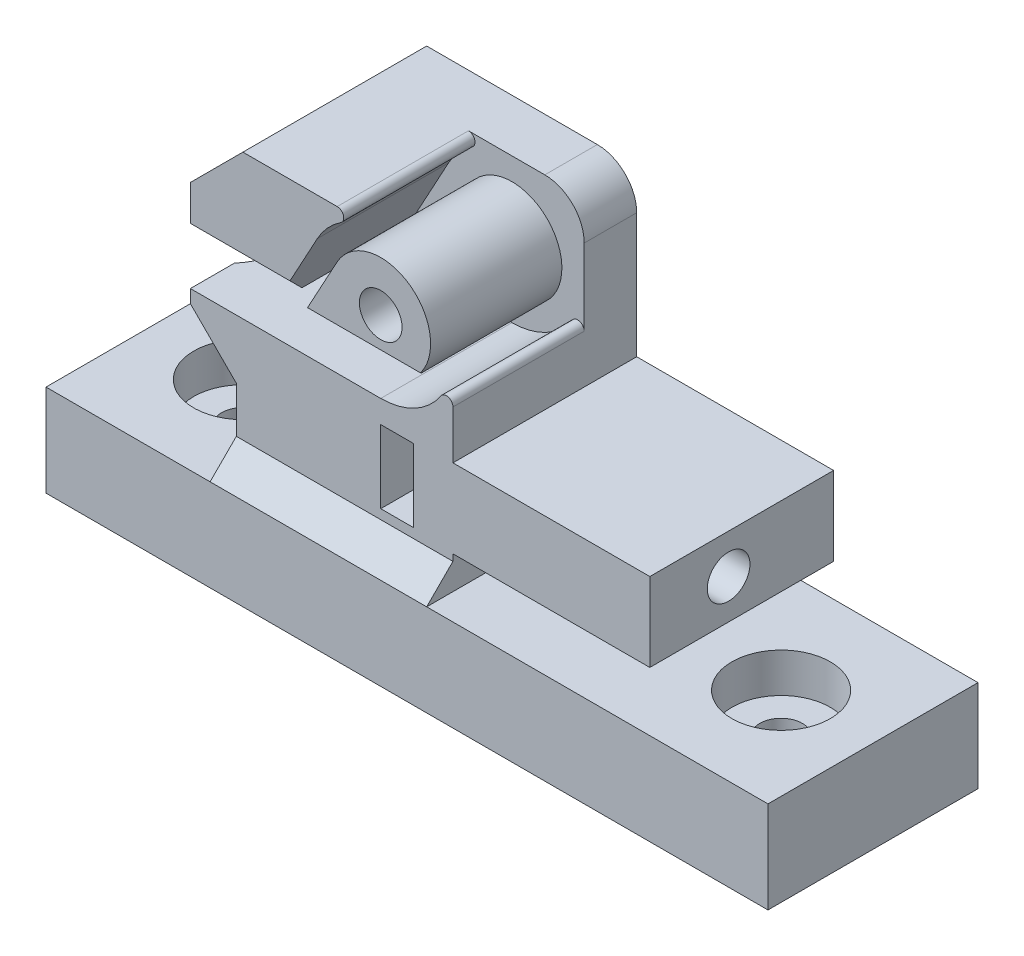
SolidWorks part; units mm, degrees
ref_plane "Front Plane" through (0, 0, 0) normal (0, 0, 1) x (1, 0, 0)
ref_plane "Top Plane" through (0, 0, 0) normal (0, 1, 0) x (1, 0, 0)
ref_plane "Right Plane" through (0, 0, 0) normal (1, 0, 0) x (0, 0, -1)
ref_plane "Plane1" [suppressed] through (25.5, 0, 0) normal (1, 0, 0) x (0, 0, -1)
sketch "Sketch4" plane through (0, 0, 0) normal (0, 0, 1) x (1, 0, 0)
  line L0 (-3.5, -0.0261) -> (-3.5, 6.9739)
  line L1 (-3.5, 6.9739) -> (9, 6.9739)
  line L4 (9, 6.9739) -> (9, 12.4739)
  line L5 (5.5, 27.9739) -> (5.5, 12.4739)
  line L8 (5.5, 27.9739) -> (25.5, 27.9739)
  line L9 (25.5, 27.9739) -> (25.5, 15.4739)
  line L10 (25.5, 15.4739) -> (40.5, 15.4739)
  line L11 (40.5, 15.4739) -> (40.5, 9.4739)
  line L12 (40.5, 9.4739) -> (25.5, 9.4739)
  line L13 (25.5, 9.4739) -> (25.5, 6.9739)
  line L14 (9, 12.4739) -> (5.5, 12.4739)
  line L16 (25.5, 6.9739) -> (51.5, 6.9739)
  line L17 (51.5, 6.9739) -> (51.5, -0.0261)
  line L18 (51.5, -0.0261) -> (-3.5, -0.0261)
  dimension "D1" = 7
  dimension "D2" = 3.5
  dimension "D3" = 26
  dimension "D4" = 29
  dimension "D5" = 28
  dimension "D6" = 15
  dimension "D10" = 6
  dimension "D11" = 12.5
  dimension "D12" = 20
  dimension "D13" = 15.5
extrude "Boss-Extrude1" add sketch "Sketch4" against normal blind 16 separate body
sketch "Sketch6" plane through (0, 0, 0) normal (0, 0, 1) x (1, 0, 0)
  line L0 (5.5, 19.2739) -> (12, 19.2739)
  line L1 (13.6088, 18.6739) -> (16.6615, 24.2889)
  line L2 (25.5, 27.9739) -> (20, 27.9739)
  line L3 (20, 18.6739) -> (13.6088, 18.6739)
  line L4 (25.5, 27.9739) -> (25.5, 22.4736)
  line L6 (5.5, 27.9739) -> (5.5, 12.4739) construction
  line L7 (25.5, 27.9739) -> (5.5, 27.9739) construction
  line L8 (5.5, 19.2739) -> (5.5, 16.9739)
  line L9 (12, 19.2739) -> (15.1679, 25.1009)
  line L10 (5.5, 16.9739) -> (20, 16.9739)
  line L15 (25.5, 15.4739) -> (25.5, 27.9739) construction
  arc A0 (20, 18.6739) -> (16.6615, 24.2889) centre (20, 22.4739) ccw
  arc A1 (20, 27.9739) -> (15.1679, 25.1009) centre (20, 22.4739) ccw
  arc A2 (20, 16.9739) -> (25.5, 22.4736) centre (20, 22.4739) ccw
  dimension "D1" = 1.7
  dimension "D2" = 5.5
  dimension "D4" = 6.5
  dimension "D3" = 2.3
extrude "Cut-Extrude1" cut sketch "Sketch6" against normal blind 14 from offset 2
sketch "Sketch7" plane through (40.5, 0, 0) normal (1, 0, 0) x (0, 0, -1)
  line L2 (0, 9.4739) -> (0, 15.4739) construction
  line L3 (16, 9.4739) -> (0, 9.4739) construction
  circle A0 centre (8, 12.4739) radius 1.625
  point P8 (0, 12.4739)
  point P10 (8, 9.4739)
  dimension "D1" = 3.25
extrude "Cut-Extrude2" cut sketch "Sketch7" against normal through all
sketch "Sketch8" plane through (40.5, 0, 0) normal (1, 0, 0) x (0, 0, -1)
  line L0 (0, 15.2489) -> (0, 9.6989)
  line L1 (0, 9.6989) -> (10.869, 9.6989)
  line L2 (5.131, 9.6989) -> (5.131, 15.2489) construction
  line L3 (0, 15.2489) -> (10.869, 15.2489)
  line L4 (10.869, 9.6989) -> (10.869, 15.2489)
  line L5 (5.131, 9.6989) -> (10.869, 15.2489) construction
  line L6 (5.131, 15.2489) -> (10.869, 9.6989) construction
  line L8 (0, 9.4739) -> (0, 15.4739) construction
  point P0 (8, 12.4739)
  dimension "D1" = 5.55
extrude "Cut-Extrude3" cut sketch "Sketch8" against normal blind 2.5 from offset 18 offset against normal yes
sketch "Sketch9" plane through (0, -0.0261, 0) normal (0, -1, 0) x (1, 0, 0)
  line L0 (-3.5, -16) -> (-3.5, 0) construction
  circle A0 centre (3.5, -8) radius 1.625
  circle A1 centre (44.5, -8) radius 1.625
  point P7 (-3.5, -8)
  dimension "D1" = 3.25
  dimension "D2" = 41
  dimension "D3" = 7
extrude "Cut-Extrude4" cut sketch "Sketch9" against normal blind 8
sketch "Sketch16" plane through (0, 6.9739, 0) normal (0, 1, 0) x (1, 0, 0)
  circle A0 centre (3.5, 8) radius 3.75
  circle A1 centre (44.5, 8) radius 3.75
  dimension "D1" = 7.5
extrude "Cut-Extrude9" cut sketch "Sketch16" against normal blind 3
sketch "Sketch21" plane through (0, 0, 0) normal (0, 0, 1) x (1, 0, 0)
  line L1 (51.5, 6.9739) -> (25.5, 6.9739) construction
  line L2 (5.5, 27.9739) -> (40.5, 27.9739)
  line L3 (5.5, 27.9739) -> (5.5, 6.9739)
  line L4 (5.5, 6.9739) -> (40.5, 6.9739)
  line L5 (40.5, 27.9739) -> (40.5, 6.9739)
extrude "Cut-Extrude13" cut sketch "Sketch21" against normal blind 2
fillet "Fillet2" radius 0.5 2 edges at (20, 27.9739, -7) (25.5, 22.4736, -7)
fillet "Fillet3" radius 3 1 edges at (25.5, 27.9739, -14)
fillet "Fillet4" radius 1 1 edges at (13.6088, 18.6739, -7)
chamfer "Chamfer3" distance 3.5 angle 45 2 edges at (5.5, 12.4739, -4.1875) (5.5, 12.4739, -12.8125)
chamfer "Chamfer4" distance 4 angle 45 1 edges at (5.5, 27.9739, -9)
sketch "Sketch18" plane through (0, 0, 0) normal (0, 0, 1) x (1, 0, 0)
  circle A0 centre (20, 22.4739) radius 1.625
  dimension "D1" = 3.25
extrude "Cut-Extrude11" cut sketch "Sketch18" against normal blind 20
sketch "Sketch19" plane through (0, 16.9739, 0) normal (0, 1, 0) x (1, 0, 0)
  line L1 (-3.5, 16) -> (-3.5, 0) construction
  line L2 (5.5, 2) -> (5.5, 16) construction
  circle A0 centre (2.5, 8) radius 4
  point P9 (-3.5, 8)
  dimension "D1" = 3
  dimension "D2" = 8
extrude "Cut-Extrude12" cut sketch "Sketch19" against normal blind 5
chamfer "Chamfer9" distance 2 angle 45 1 edges at (17.25, 6.9739, -2)
chamfer "Chamfer12" distance 1.5 angle 45 1 edges at (17.6453, 18.6739, -2)
chamfer "Chamfer11" distance 2 angle 45 1 edges at (8.75, 19.2739, -2)
delete or keep bodies "Body-Delete/Keep 2" [suppressed] type delete bodies bodies 107
sketch "Sketch10" plane through (25.5, 0, 0) normal (1, 0, 0) x (0, 0, -1)
  line L0 (-1.5, 7.4739) -> (15.5, 7.4739)
  line L1 (15.5, 7.4739) -> (15.5, 27.9739)
  line L2 (15.5, 27.9739) -> (-1.5, 27.9739)
  line L3 (-1.5, 27.9739) -> (-1.5, 7.4739)
  dimension "D1" = 20.5
  dimension "D2" = 17
extrude "Boss-Extrude2" [suppressed] add sketch "Sketch10" along normal blind 20
sketch "Sketch11" [suppressed] plane through (0, 0, 1.5) normal (0, 0, 1) x (1, 0, 0)
  line L0 (31, 16.9739) -> (45.5, 16.9739)
  line L1 (45.5, 27.9739) -> (45.5, 7.4739) construction
  line L2 (39.8796, 19.2739) -> (35.5305, 25.5923)
  line L3 (45.5, 19.2739) -> (45.5, 16.9739)
  line L4 (25.5, -8.25) -> (25.5, 8.25) construction
  line L5 (25.5, 27.9739) -> (25.5, 7.4739) construction
  line L6 (45.5, 27.9739) -> (25.5, 27.9739) construction
  line L7 (39.8796, 19.2739) -> (45.5, 19.2739)
  line L8 (31, 27.9739) -> (25.5, 27.9739)
  line L9 (25.5, 27.9739) -> (25.5, 22.4739)
  line L11 (31, 18.6739) -> (38.2288, 18.6739)
  line L13 (38.2288, 18.6739) -> (34.1302, 24.6284)
  arc A0 (35.5305, 25.5923) -> (31, 27.9739) centre (31, 22.4739) ccw
  arc A1 (25.5, 22.4739) -> (31, 16.9739) centre (31, 22.4739) ccw
  arc A2 (34.1302, 24.6284) -> (31, 18.6739) centre (31, 22.4739) ccw
  dimension "D1" = 11
  dimension "D4" = 7.6
  dimension "D3" = 2.3
extrude "Cut-Extrude5" [suppressed] cut sketch "Sketch11" against normal blind 11.5
sketch "Sketch12" [suppressed] plane through (45.5, 0, 0) normal (1, 0, 0) x (0, 0, -1)
  line L2 (-1.5, 16.9739) -> (-1.5, 7.4739) construction
  line L3 (-1.5, 7.4739) -> (15.5, 7.4739) construction
  circle A0 centre (6, 12.4739) radius 1.625
  dimension "D1" = 3.25
  dimension "D2" = 7.5
  dimension "D3" = 5
extrude "Cut-Extrude6" [suppressed] cut sketch "Sketch12" against normal blind 20 contours A0
sketch "Sketch14" [suppressed] plane through (25.5, 0, 0) normal (-1, 0, 0) x (0, 0, 1)
  line L0 (1.5, 7.4739) -> (-15.5, 7.4739) construction
  line L1 (0.3, 9.1739) -> (-14.3, 9.1739)
  line L2 (0.3, 9.1739) -> (0.3, 15.7739)
  line L3 (0.3, 15.7739) -> (-14.3, 15.7739)
  line L4 (-14.3, 9.1739) -> (-14.3, 15.7739)
  line L5 (1.5, 22.4739) -> (1.5, 7.4739) construction
  line L6 (-15.5, 7.4739) -> (-15.5, 27.9739) construction
  dimension "D1" = 1.7
  dimension "D2" = 1.2
  dimension "D3" = 1.2
  dimension "D4" = 6.6
extrude "Cut-Extrude7" [suppressed] cut sketch "Sketch14" against normal blind 20
sketch "Sketch22" [suppressed] plane through (0, 0, 1.5) normal (0, 0, 1) x (1, 0, 0)
  line L0 (25.5, 27.9739) -> (25.5, 22.4739) construction
  line L1 (25.5, 27.9739) -> (45.5, 27.9739)
  line L2 (25.5, 27.9739) -> (25.5, 16.9739)
  line L3 (25.5, 16.9739) -> (45.5, 16.9739)
  line L4 (45.5, 27.9739) -> (45.5, 16.9739)
  line L5 (31, 27.9739) -> (25.5, 27.9739) construction
  line L6 (45.5, 16.9739) -> (45.5, 7.4739) construction
  line L7 (31, 16.9739) -> (45.5, 16.9739) construction
extrude "Cut-Extrude14" [suppressed] cut sketch "Sketch22" against normal blind 1.5
chamfer "Chamfer5" [suppressed] distance 4 angle 45
chamfer "Chamfer6" [suppressed] distance 2 angle 45
chamfer "Chamfer7" [suppressed] distance 1.5 angle 45
fillet "Fillet6" [suppressed] radius 1
fillet "Fillet7" [suppressed] radius 3
fillet "Fillet5" [suppressed] radius 0.5
sketch "Sketch15" [suppressed] plane through (45.5, 0, 0) normal (1, 0, 0) x (0, 0, -1)
  circle A0 centre (6, 12.4739) radius 3.75
  dimension "D1" = 7.5
extrude "Cut-Extrude8" [suppressed] cut sketch "Sketch15" against normal blind 1.75
chamfer "Chamfer8" [suppressed] distance 0.75 angle 45
sketch "Sketch17" [suppressed] plane through (0, 0, 1.5) normal (0, 0, 1) x (1, 0, 0)
  circle A0 centre (31, 22.4739) radius 1.625
  dimension "D1" = 3.25
extrude "Cut-Extrude10" [suppressed] cut sketch "Sketch17" against normal blind 20
chamfer "Chamfer10" [suppressed] distance 1.5 angle 45
sketch "Sketch23" [suppressed] plane through (0, 0, -15.5) normal (0, 0, -1) x (-1, 0, 0)
  circle A0 centre (-31, 22.4739) radius 3.75
  dimension "D1" = 7.5
extrude "Cut-Extrude15" [suppressed] cut sketch "Sketch23" against normal blind 1.5
